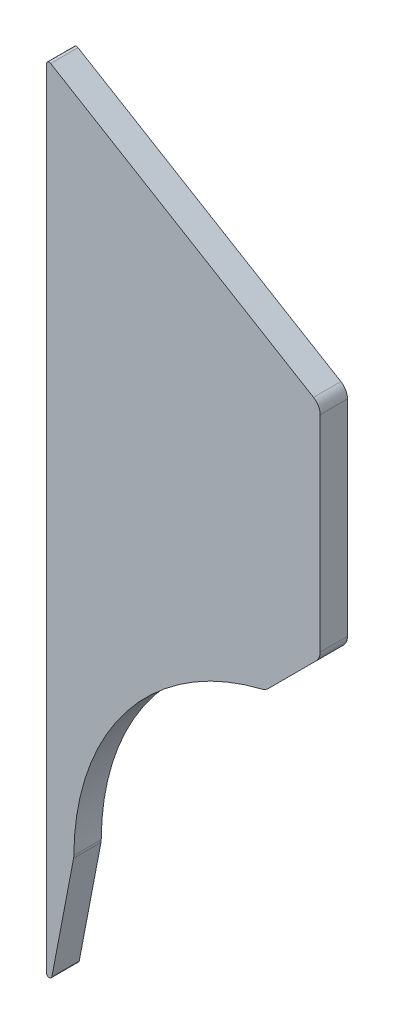
SolidWorks part; units mm, degrees
ref_plane "Front Plane" through (0, 0, 0) normal (0, 0, 1) x (1, 0, 0)
ref_plane "Top Plane" through (0, 0, 0) normal (0, 1, 0) x (1, 0, 0)
ref_plane "Right Plane" through (0, 0, 0) normal (1, 0, 0) x (0, 0, -1)
sketch "Sketch1" plane through (0, 0, 0) normal (0, 0, 1) x (1, 0, 0)
  line L0 (1.5145, 99.0913) -> (97.5725, 41.4565)
  line L1 (600, 40) -> (0, 40) construction
  line L2 (100, 37.169) -> (100, -37.9289)
  line L3 (600, -40) -> (0, -40) construction
  line L5 (600, -50) -> (0, -50) construction
  line L6 (0, -190) -> (0, 90) construction
  line L7 (10, -52.9377) -> (10, -147.7496) construction
  line L9 (9.9121, -148.209) -> (1.9822, -189.6431)
  line L10 (0, -189.4551) -> (0, 98.2338)
  line L11 (100, -40) -> (80, -40) construction
  line L12 (80, -40) -> (80, -60) construction
  line L13 (98.5355, -41.4645) -> (81.0043, -58.9957)
  arc A0 (78.6546, -60.3175) -> (10.0012, -147.2944) centre (100, -147.7496) ccw
  arc A1 (1.9822, -189.6431) -> (0, -189.4551) centre (1, -189.4551) cw
  arc A2 (1.5145, 99.0913) -> (0, 98.2338) centre (1, 98.2338) ccw
  arc A3 (10.0012, -147.2944) -> (9.9121, -148.209) centre (5.0012, -147.2691) cw
  arc A4 (78.6546, -60.3175) -> (81.0043, -58.9957) centre (77.4687, -55.4602) ccw
  arc A5 (97.5725, 41.4565) -> (100, 37.169) centre (95, 37.169) cw
  arc A6 (100, -37.9289) -> (98.5355, -41.4645) centre (95, -37.9289) cw
  point P21 (0, -200)
  point P24 (0, 100)
  point P33 (100, 40)
  dimension "D3" = 1
  dimension "D4" = 5
  dimension "D5" = 100
  dimension "D6" = 5
  dimension "D7" = 5
  dimension "D1" = 10
  dimension "D2" = 10
extrude "Boss-Extrude1" add sketch "Sketch1" along normal blind 10
